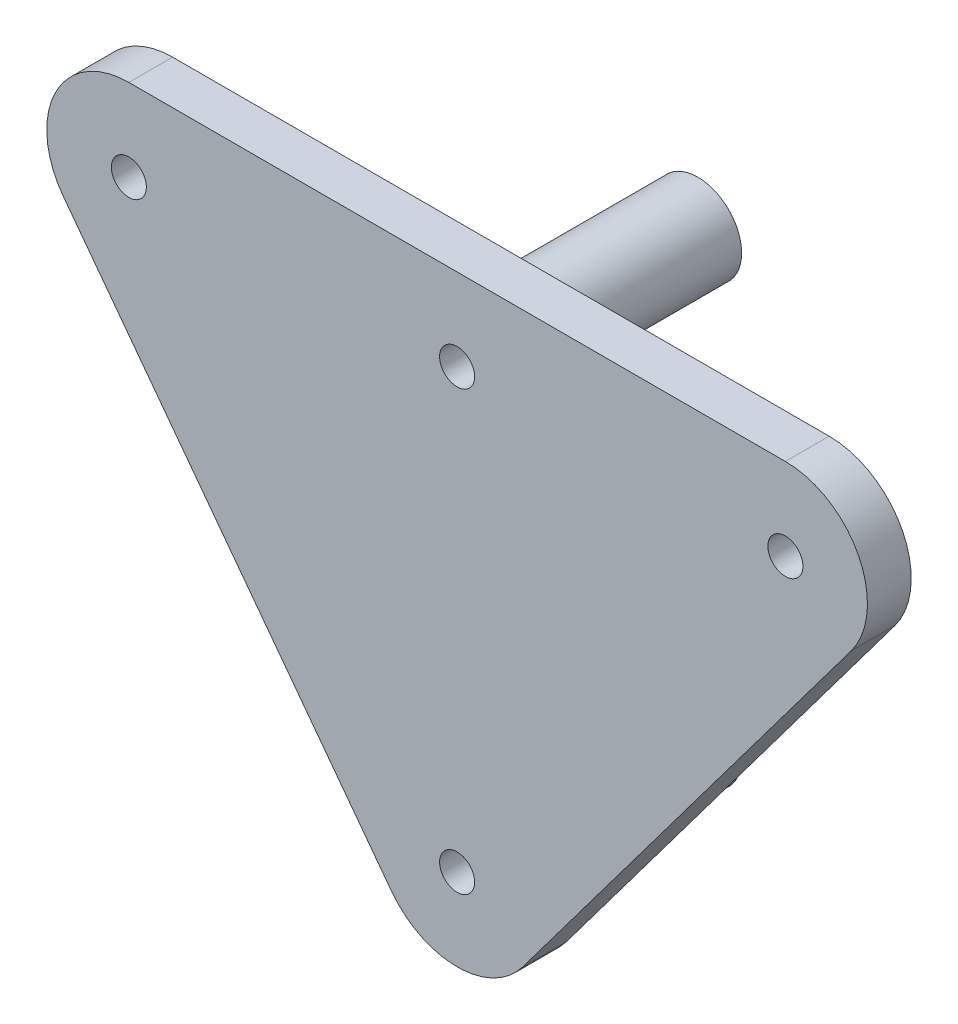
SolidWorks part; units mm, degrees
ref_plane "Front Plane" through (0, 0, 0) normal (0, 0, 1) x (1, 0, 0)
ref_plane "Top Plane" through (0, 0, 0) normal (0, 1, 0) x (1, 0, 0)
ref_plane "Right Plane" through (0, 0, 0) normal (1, 0, 0) x (0, 0, -1)
ref_axis "X" through (-88.99, 0, 0) along (1, 0, 0)
ref_axis "Y" through (0, 55, 0) along (0, -1, 0)
ref_axis "Z" through (0, 0, -88.99) along (0, 0, 1)
sketch "Sketch1" plane through (0, 0, 0) normal (0, 0, 1) x (1, 0, 0)
  line L0 (-36, 15.5) -> (-6, -24.5)
  line L1 (6, -24.5) -> (36, 15.5)
  line L2 (-30, 27.5) -> (30, 27.5)
  circle A0 centre (-30, 20) radius 7.5
  circle A1 centre (30, 20) radius 7.5
  circle A2 centre (0, -20) radius 7.5
  circle A3 centre (0, 20) radius 7.5
  circle A4 centre (0, 20) radius 4
  circle A5 centre (0, -20) radius 4
  circle A6 centre (-30, 20) radius 1.6
  circle A7 centre (0, 20) radius 1.6
  circle A8 centre (0, -20) radius 1.6
  circle A9 centre (30, 20) radius 1.6
  dimension "D1" = 15
  dimension "D2" = 8
  dimension "D3" = 3.2
extrude "Boss-Extrude1" add sketch "Sketch1" along normal blind 4 contours A0 | L2 A3 A0 L0 A2 L1 A1 | A1 | A2 A5 | A3 A4 | A4 | A5 region at (5.1533, 25.1533, 0) region at (0, 6.0857, 0) region at (-36.5185, 23.2592, 0) region at (-2.3046, -13.0861, 0) region at (23.4815, 16.7408, 0) region at (-3.8869, 20, 0) region at (-3.8869, -20, 0)
extrude "Boss-Extrude2" add sketch "Sketch1<4>" against normal up to surface (18 mm away) contours A4 A7 | A5 A8 region at (-3.8869, 20, 0) region at (-3.8869, -20, 0)
sketch "Sketch1<4>" plane through (0, 0, 0) normal (0, 0, 1) x (1, 0, 0) same geometry as "Sketch1"
sketch "Sketch3" plane through (0, 0, 0) normal (0, 0, -1) x (-1, 0, 0)
  circle A0 centre (30, 20) radius 1.6 construction
  circle A1 centre (-30, 20) radius 1.6 construction
  circle A2 centre (30, 20) radius 1.6
  circle A3 centre (-30, 20) radius 1.6
  circle A4 centre (-30, 20) radius 3.6
  circle A5 centre (30, 20) radius 3.6
  dimension "D1" = 2
extrude "Boss-Extrude3" add sketch "Sketch3" along normal blind 0.5
fillet "Fillet1" radius 2 2 edges at (4, -20, 0) (4, 20, 0)
